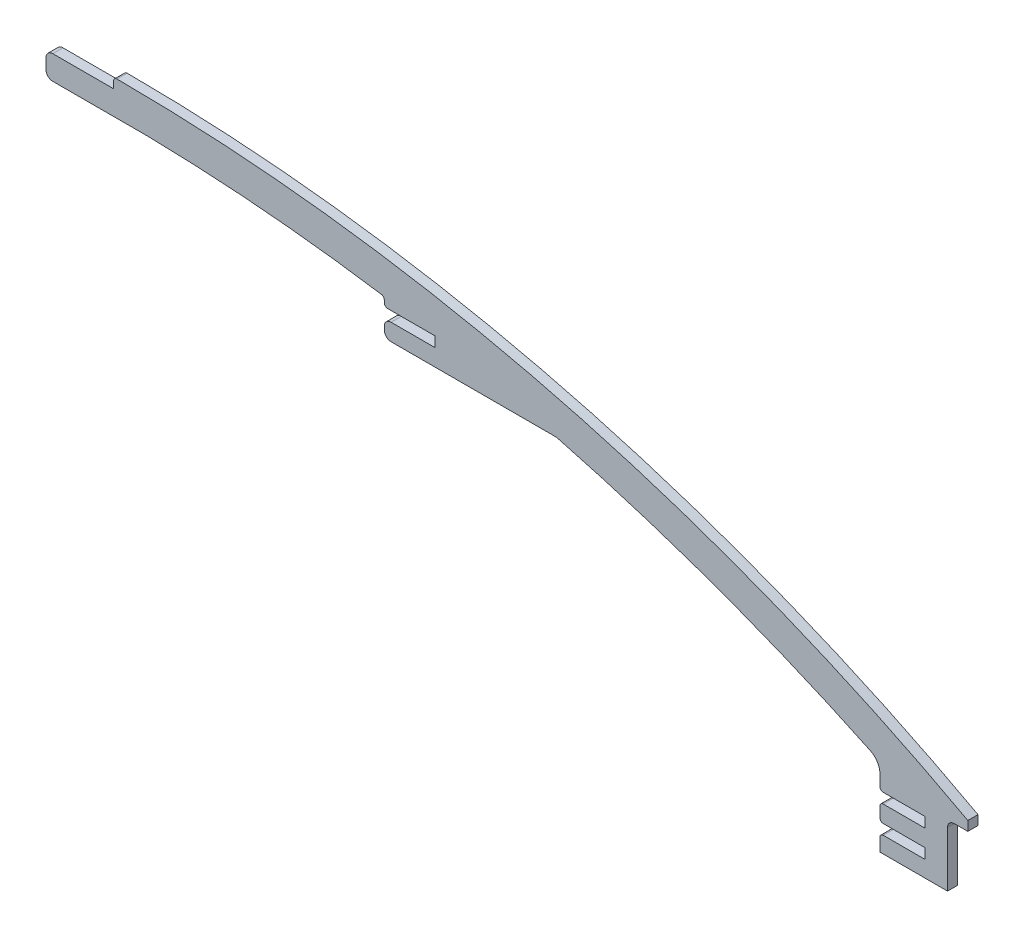
SolidWorks part; units mm, degrees
ref_plane "Front Plane" through (0, 0, 0) normal (0, 0, 1) x (1, 0, 0)
ref_plane "Top Plane" through (0, 0, 0) normal (0, 1, 0) x (1, 0, 0)
ref_plane "Right Plane" through (0, 0, 0) normal (1, 0, 0) x (0, 0, -1)
sketch "Sketch1" plane through (0, 0, 0) normal (0, 0, 1) x (1, 0, 0)
  line L0 (-45, 0) -> (45, 0) construction
  line L1 (300, -65.3534) -> (300, -85.3534)
  line L2 (-45, -150.7069) -> (45, -150.7069) construction
  line L3 (-45, 0) -> (-45, -150.7069) construction
  line L4 (45, 0) -> (45, -150.7069) construction
  line L5 (0, 0) -> (0, -150.7069)
  line L6 (45, 0) -> (0, 0)
  line L7 (0, -150.7069) -> (45, -150.7069)
  arc A0 (45, 0) -> (300, -65.3534) centre (45, -530.1639) cw
  arc A1 (-28.1177, 0) -> (35.3823, 0) centre (3.6323, -0.0236) cw construction
  arc A2 (45, -150.7069) -> (300, -85.3534) centre (45, 379.457) ccw
  point P4 (0, 0)
  dimension "D2" = 300
  dimension "D3" = 31.75
  dimension "D5" = 150.7069
  dimension "D1" = 90
  dimension "D4" = 20
sketch "Sketch2" plane through (0, 0, 0) normal (0, 0, 1) x (1, 0, 0)
  line L0 (299.5, -67.3534) -> (293.5, -67.3534)
  line L1 (291.5, -69.3534) -> (291.5, -85.6495)
  line L2 (54.9033, -10.5962) -> (27, -10.5962)
  line L3 (25, -8.5962) -> (25, -5.5)
  line L4 (300, -65.3534) -> (300, -85.3534) construction
  line L5 (300, -65.3534) -> (300, -85.3534) construction
  line L6 (299.5, -65.6495) -> (299.5, -67.3534)
  line L7 (291.5, -85.6495) -> (271.5, -85.6495)
  line L8 (45, -1.5009) -> (45, -3.5)
  line L9 (45, 0) -> (45, -150.7069) construction
  line L10 (45, -3.5) -> (27, -3.5)
  line L11 (271.5, -85.6495) -> (271.5, -65.6032)
  line L12 (45, -0.5) -> (0.5, -0.5)
  line L13 (0.5, -0.5) -> (0.5, -150.2069)
  line L14 (0.5, -150.2069) -> (45, -150.2069)
  line L15 (299.5, -85.0574) -> (299.5, -65.6495)
  line L20 (55, -13.5) -> (25, -13.5) construction
  line L21 (55, -10.5962) -> (55, -13.5) construction
  line L22 (140, -19.2573) -> (140, -23.2573)
  line L23 (140, -19.2573) -> (126, -19.2573)
  line L24 (125, -18.2573) -> (125, -17.5517)
  line L25 (141, -24.2573) -> (163.7816, -24.2573)
  line L26 (0, 0) -> (0, -150.7069) construction
  line L27 (45, -3.5) -> (25, -3.5) construction
  line L28 (45, -0.5) -> (45, -3.5) construction
  arc A0 (268.6519, -61.0899) -> (163.7816, -24.2573) centre (45, -530.1639) ccw
  arc A1 (294.6951, -74.4195) -> (55, -10.5962) centre (45, -530.1639) ccw construction
  arc A2 (55.0976, -10.5981) -> (54.9033, -10.5962) centre (54.9033, -20.5962) ccw
  arc A3 (271.5, -65.6032) -> (268.6519, -61.0899) centre (266.5, -65.6032) ccw
  arc A4 (293.5, -67.3534) -> (291.5, -69.3534) centre (293.5, -69.3534) ccw
  arc A5 (124.1523, -16.5634) -> (55.0976, -10.5981) centre (45, -530.1639) ccw
  arc A6 (45, -150.2069) -> (299.5, -85.0574) centre (45, 379.457) ccw
  arc A7 (299.5, -65.6495) -> (45, -0.5) centre (45, -530.1639) ccw
  arc A9 (299.5, -65.6495) -> (46.0019, -0.5009) centre (45, -530.1639) ccw
  arc A10 (125, -16.6947) -> (163.7816, -24.2573) centre (45, -530.1639) cw construction
  arc A11 (140, -23.2573) -> (141, -24.2573) centre (141, -23.2573) ccw
  arc A12 (126, -19.2573) -> (125, -18.2573) centre (126, -18.2573) cw
  arc A13 (125, -17.5517) -> (124.1523, -16.5634) centre (124, -17.5517) ccw
  arc A14 (27, -10.5962) -> (25, -8.5962) centre (27, -8.5962) cw
  arc A15 (27, -3.5) -> (25, -5.5) centre (27, -5.5) ccw
  arc A16 (299.5, -65.6495) -> (45, -0.5) centre (45, -530.1639) ccw construction
  arc A17 (45, -1.5009) -> (46.0019, -0.5009) centre (46, -1.5009) cw
  point P26 (300, -75.3534)
  point P33 (291.5, -67.3534)
  point P43 (140, -24.2573)
  point P48 (125, -19.2573)
  point P57 (25, -3.5)
  dimension "D5" = 10
  dimension "D10" = 5
  dimension "D11" = 2
  dimension "D16" = 1
  dimension "D17" = 2
  dimension "D18" = 1
  dimension "D2" = 20
  dimension "D3" = 3
  dimension "D6" = 7.0962
  dimension "D7" = 8
  dimension "D8" = 8
  dimension "D9" = 20
  dimension "D12" = 20
  dimension "D13" = 15
  dimension "D14" = 5
  dimension "D15" = 140
  dimension "D1" = 0.5
  dimension "D4" = 10
extrude "Boss-Extrude1" add sketch "Sketch2" along normal mid plane 3
sketch "Sketch3" plane through (0, 0, 1.5) normal (0, 0, 1) x (1, 0, 0)
  line L0 (300, -75.3534) -> (270.8122, -75.3534) construction
  line L1 (300, -65.3534) -> (300, -85.3534) construction
  line L3 (271.5, -69.8534) -> (284.8, -69.8534)
  line L4 (271.5, -69.8534) -> (271.5, -72.8534)
  line L5 (271.5, -72.8534) -> (284.8, -72.8534)
  line L6 (284.8, -69.8534) -> (284.8, -72.8534)
  line L7 (271.5, -65.6032) -> (271.5, -85.6495) construction
  line L8 (284.8, -80.8534) -> (284.8, -77.8534)
  line L9 (271.5, -77.8534) -> (284.8, -77.8534)
  line L10 (271.5, -80.8534) -> (271.5, -77.8534)
  line L11 (271.5, -80.8534) -> (284.8, -80.8534)
  point P10 (284.8, -71.3534)
  dimension "D1" = 13.3
  dimension "D2" = 4
  dimension "D3" = 3
extrude "Cut-Extrude1" cut sketch "Sketch3" against normal blind 10
fillet "Fillet1" radius 1 4 edges at (271.5, -80.8534, 0) (271.5, -77.8534, 0) (271.5, -72.8534, 0) (271.5, -69.8534, 0)
sketch "Sketch4" plane through (0, 0, 1.5) normal (0, 0, 1) x (1, 0, 0)
  line L0 (299.5, -67.3534) -> (299.5, -65.6495) construction
  line L1 (297.5, -62.5957) -> (299.5, -62.5957)
  line L2 (297.5, -62.5957) -> (297.5, -69.6147)
  line L3 (297.5, -69.6147) -> (299.5, -69.6147)
  line L4 (299.5, -62.5957) -> (299.5, -69.6147)
  dimension "D1" = 2
extrude "Cut-Extrude2" cut sketch "Sketch4" against normal blind 10
sketch "Sketch5" plane through (0, 0, 1.5) normal (0, 0, 1) x (1, 0, 0)
  line L0 (140, -19.2573) -> (140, -22.2573)
  line L1 (140, -22.2573) -> (127, -22.2573)
  line L2 (125, -24.2573) -> (125, -25.2573)
  line L3 (127, -27.2573) -> (175.9027, -27.2573)
  line L4 (175.9027, -27.2573) -> (184.7562, -23.3114)
  line L5 (184.7562, -23.3114) -> (140, -19.2573)
  line L6 (126, -19.2573) -> (140, -19.2573) construction
  line L7 (125, -17.5517) -> (125, -18.2573) construction
  arc A0 (268.6519, -61.0899) -> (163.7816, -24.2573) centre (45, -530.1639) ccw construction
  arc A1 (125, -25.2573) -> (127, -27.2573) centre (127, -25.2573) ccw
  arc A2 (127, -22.2573) -> (125, -24.2573) centre (127, -24.2573) ccw
  dimension "D3" = 2
  dimension "D1" = 3
  dimension "D2" = 5
extrude "Boss-Extrude2" add sketch "Sketch5" against normal up to surface (3 mm away) up to face at (190.1757, -45.0815, -1.5)
